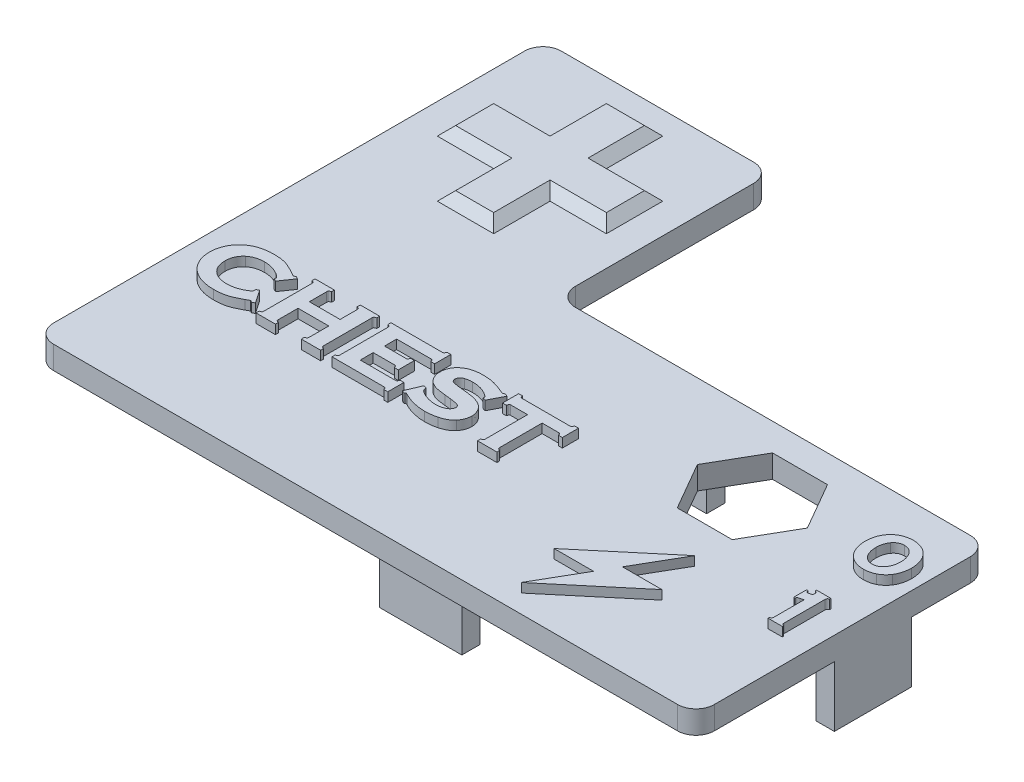
SolidWorks part; units mm, degrees
ref_plane "Front" through (0, 0, 0) normal (0, 0, 1) x (1, 0, 0)
ref_plane "Top" through (0, 0, 0) normal (0, 1, 0) x (1, 0, 0)
ref_plane "Right" through (0, 0, 0) normal (1, 0, 0) x (0, 0, -1)
sketch "Sketch1" plane through (0, 0, 0) normal (0, 1, 0) x (1, 0, 0)
  line L0 (-36.05, 15.975) -> (-36.05, 39.425)
  line L1 (-36.05, -15.975) -> (36.05, -15.975)
  line L2 (-36.05, -15.975) -> (-36.05, 15.975)
  line L3 (-11.05, 15.975) -> (36.05, 15.975)
  line L4 (36.05, -15.975) -> (36.05, 15.975)
  line L5 (-36.05, -15.975) -> (36.05, 15.975) construction
  line L6 (-36.05, 15.975) -> (36.05, -15.975) construction
  line L7 (-36.05, 39.425) -> (-11.05, 39.425)
  line L8 (-11.05, 39.425) -> (-11.05, 15.975)
  point P0 (0, 0)
  dimension "D1" = 31.95
  dimension "D2" = 72.1
  dimension "D3" = 25
  dimension "D4" = 55.4
extrude "Boss-Extrude1" add sketch "Sketch1" along normal blind 2.5
fillet "Fillet1" radius 2 6 edges at (36.05, 1.25, -15.975) (36.05, 1.25, 15.975) (-36.05, 1.25, 15.975) (-11.05, 1.25, -15.975) (-11.05, 1.25, -39.425) (-36.05, 1.25, -39.425)
sketch "Sketch2" plane through (0, 0, 0) normal (0, -1, 0) x (1, 0, 0)
  line L0 (36.05, 13.975) -> (36.05, -13.975) construction
  line L1 (34.05, -7.525) -> (36.05, -7.525)
  line L2 (34.05, -7.525) -> (34.05, 0.875)
  line L3 (34.05, 0.875) -> (36.05, 0.875)
  line L4 (36.05, -7.525) -> (36.05, 0.875)
  line L5 (34.05, -7.525) -> (36.05, 0.875) construction
  line L6 (34.05, 0.875) -> (36.05, -7.525) construction
  line L7 (35.05, -7.575) -> (35.05, 0.925) construction
  line L8 (35.05, 0.925) -> (35.05, 15.975) construction
  line L9 (-34.05, 15.975) -> (34.05, 15.975) construction
  line L10 (34.05, -15.975) -> (-9.05, -15.975) construction
  line L11 (8.5, -14.725) -> (-0.5, -14.725)
  line L12 (8.5, -14.725) -> (8.5, -12.725)
  line L13 (8.5, -12.725) -> (-0.5, -12.725)
  line L14 (-0.5, -14.725) -> (-0.5, -12.725)
  line L15 (8.5, -14.725) -> (-0.5, -12.725) construction
  line L16 (8.5, -12.725) -> (-0.5, -14.725) construction
  line L17 (8.5, 11.975) -> (-0.5, 11.975)
  line L18 (8.5, 11.975) -> (8.5, 13.975)
  line L19 (8.5, 13.975) -> (-0.5, 13.975)
  line L20 (-0.5, 11.975) -> (-0.5, 13.975)
  line L21 (8.5, 11.975) -> (-0.5, 13.975) construction
  line L22 (8.5, 13.975) -> (-0.5, 11.975) construction
  line L23 (0, 0) -> (-50000, 0) construction
  point P0 (35.05, -3.325)
  point P7 (35.05, -3.325)
  point P13 (4, -13.725)
  point P18 (4, 12.975)
  dimension "D1" = 2
  dimension "D2" = 8.4
  dimension "D3" = 15.05
  dimension "D4" = 8.5
  dimension "D5" = 2
  dimension "D6" = 1.25
  dimension "D7" = 2
  dimension "D8" = 0.5
  dimension "D9" = 9
extrude "Boss-Extrude2" add sketch "Sketch2" along normal blind 6.6
sketch "Sketch3" plane through (0, 2.5, 0) normal (0, 1, 0) x (1, 0, 0)
  line L0 (-22.8, 6.025) -> (-7.8, 6.025) construction
  line L1 (-34.05, -2.975) -> (3.45, -2.975) construction
  line L2 (29.55, 6.025) -> (36.05, 6.025) construction
  line L9 (21.9141, -1.975) -> (19.0274, -6.975)
  line L11 (17.8726, -8.975) -> (14.9859, -13.975)
  line L12 (14.9859, -13.975) -> (23.3282, -6.975)
  line L13 (23.3282, -6.975) -> (19.0274, -6.975)
  line L14 (21.9141, -1.975) -> (13.5718, -8.975)
  line L15 (13.5718, -8.975) -> (17.8726, -8.975)
  line L16 (12.7, -15.975) -> (12.7, 0.025) construction
  line L17 (-34.05, -15.975) -> (34.05, -15.975) construction
  line L18 (12.7, 0.025) -> (24.2, 0.025) construction
  line L19 (24.2, 0.025) -> (24.2, -15.975) construction
  line L20 (24.2, -15.975) -> (12.7, -15.975) construction
  line L21 (36.05, -13.975) -> (36.05, 13.975) construction
  line L22 (21.9141, -1.975) -> (14.9859, -13.975) construction
  line L23 (-26.625, 36.925) -> (-20.475, 36.925)
  line L24 (-20.475, 36.925) -> (-20.475, 30.775)
  line L25 (-36.05, 37.425) -> (-36.05, -13.975) construction
  line L26 (-20.475, 30.775) -> (-14.325, 30.775)
  line L27 (-14.325, 30.775) -> (-14.325, 24.625)
  line L28 (-14.325, 24.625) -> (-20.475, 24.625)
  line L29 (-20.475, 24.625) -> (-20.475, 18.475)
  line L30 (-20.475, 18.475) -> (-26.625, 18.475)
  line L31 (-26.625, 18.475) -> (-26.625, 24.625)
  line L32 (-26.625, 24.625) -> (-32.775, 24.625)
  line L33 (-32.775, 24.625) -> (-32.775, 30.775)
  line L34 (-32.775, 30.775) -> (-26.625, 30.775)
  line L35 (-26.625, 30.775) -> (-26.625, 36.925)
  line L36 (-11.05, 27.7) -> (-36.05, 27.7) construction
  line L37 (-11.05, 17.975) -> (-11.05, 37.425) construction
  line L38 (-36.05, 37.425) -> (-36.05, -13.975) construction
  line L39 (-13.05, 39.425) -> (-34.05, 39.425) construction
  text T0 "<b>CHEST</b>" font "Copperplate Gothic Bold" height 6.35
  text T2 "0\r\n1" font "Copperplate Gothic Bold" height in points 26
  point P18 (18.45, -7.975)
  point P19 (18.45, 0.025)
  point P20 (12.7, -7.975)
  point P38 (-32.775, 27.7)
  point P43 (-15.3, 6.025)
  point P44 (-15.3, -2.975)
  point P50 (-23.55, 36.925)
  point P51 (-23.55, 27.7)
  dimension "D1" = 40
  dimension "D2" = 20
  dimension "D3" = 2
  dimension "D4" = 5
  dimension "D5" = 11.85
  dimension "D6" = 23.35
  dimension "D7" = 2
  dimension "D8" = 6.5
  dimension "D9" = 22
  dimension "D10" = 22
  dimension "D11" = 2
  dimension "D12" = 9
  dimension "D13" = 37.5
  dimension "D14" = 15
  dimension "D15" = 2.5
extrude "Boss-Extrude3" add sketch "Sketch3" along normal blind 1
sketch "Sketch4" plane through (0, 2.5, 0) normal (0, 1, 0) x (1, 0, 0)
  line L5 (34.05, 15.975) -> (-9.05, 15.975) construction
  line L7 (18.45, 2.5827) -> (18.45, -15.975) construction
  line L9 (21.45, 2.5827) -> (24.45, 7.7788)
  line L10 (24.45, 7.7788) -> (21.45, 12.975)
  line L11 (21.45, 12.975) -> (15.45, 12.975)
  line L12 (15.45, 12.975) -> (12.45, 7.7788)
  line L13 (12.45, 7.7788) -> (15.45, 2.5827)
  line L14 (15.45, 2.5827) -> (21.45, 2.5827)
  line L15 (24.2, -15.975) -> (12.7, -15.975) construction
  circle A0 centre (18.45, 7.7788) radius 5.1962 construction
  dimension "D1" = 3
  dimension "D2" = 6
extrude "Cut-Extrude1" cut sketch "Sketch4" against normal up to vertex (2.5 mm away) up to point (34.05, 0, 15.975)
chamfer "Chamfer1" distance 1 angle 45 12 edges at (-23.55, 3.5, -36.925) (-20.475, 3.5, -33.85) (-17.4, 3.5, -30.775) (-14.325, 3.5, -27.7) (-17.4, 3.5, -24.625) (-20.475, 3.5, -21.55) (-23.55, 3.5, -18.475) (-26.625, 3.5, -21.55) (-29.7, 3.5, -24.625) (-32.775, 3.5, -27.7) (-29.7, 3.5, -30.775) (-26.625, 3.5, -33.85)
